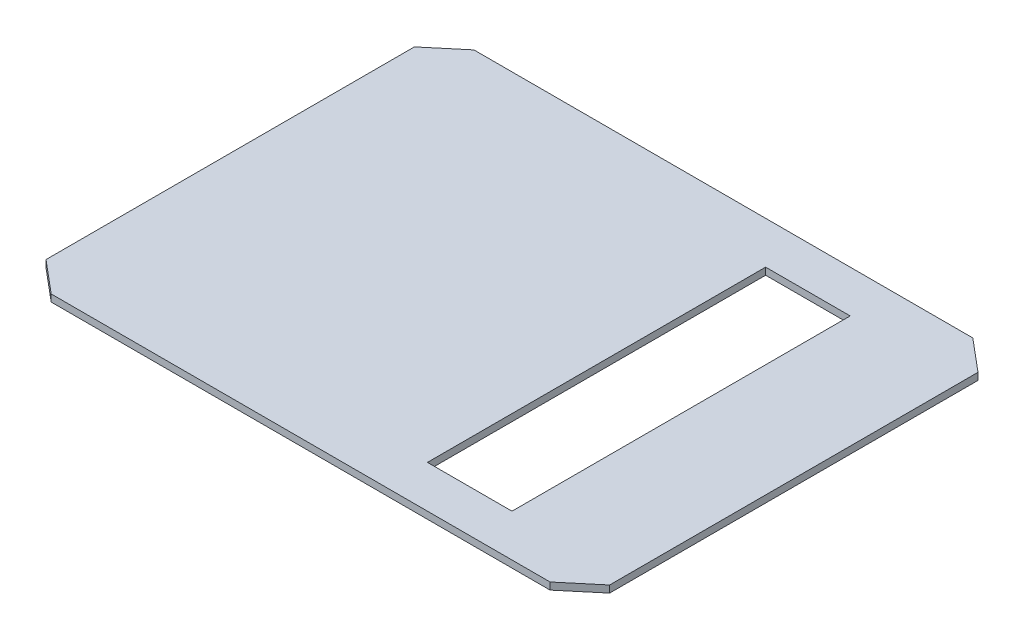
SolidWorks part; units mm, degrees
material "Thornel Mat VMA"
ref_plane "Front Plane" through (0, 0, 0) normal (0, 0, 1) x (1, 0, 0)
ref_plane "Top Plane" through (0, 0, 0) normal (0, 1, 0) x (1, 0, 0)
ref_plane "Right Plane" through (0, 0, 0) normal (1, 0, 0) x (0, 0, -1)
sketch "Sketch1" plane through (0, 0, 0) normal (0, 1, 0) x (1, 0, 0)
  line L0 (0, -95.25) -> (0, 95.25) construction
  line L1 (-127, 95.25) -> (127, 95.25) construction
  line L2 (-127, 95.25) -> (-127, -95.25) construction
  line L3 (-127, -95.25) -> (127, -95.25) construction
  line L4 (127, 95.25) -> (127, -95.25) construction
  line L5 (-127, 0) -> (127, 0) construction
  line L6 (-114.3, 0) -> (-114.3, 52.7344) construction
  line L7 (-114.3, 52.7344) -> (-101.6, 52.7344) construction
  line L8 (-101.6, 52.7344) -> (-87.0069, 64.9795) construction
  line L9 (-87.0069, 64.9795) -> (-87.0069, 76.2) construction
  line L10 (-87.0069, 76.2) -> (0, 76.2) construction
  line L11 (-127, 83.0049) -> (-112.4069, 95.25) construction
  line L12 (-87.0069, 64.9795) -> (-112.4069, 95.25) construction
  line L13 (-101.6, 52.7344) -> (-127, 83.0049) construction
  line L15 (-127, 95.25) -> (127, 95.25) construction
  line L16 (-127, 95.25) -> (-127, -95.25) construction
  line L17 (-127, -95.25) -> (127, -95.25) construction
  line L18 (127, 95.25) -> (127, -95.25) construction
  line L19 (-127, 95.25) -> (127, -95.25) construction
  line L20 (-127, -95.25) -> (127, 95.25) construction
  line L22 (127, -83.0049) -> (112.4069, -95.25)
  line L23 (-127, -83.0049) -> (-112.4069, -95.25)
  line L24 (-112.4069, 95.25) -> (112.4069, 95.25)
  line L25 (-127, -83.0049) -> (-127, 83.0049)
  line L26 (127, 83.0049) -> (127, -83.0049)
  line L27 (112.4069, -95.25) -> (-112.4069, -95.25)
  line L28 (-94.3034, 58.8569) -> (-119.7034, 89.1274) construction
  line L33 (-127, 83.0049) -> (-112.4069, 95.25)
  line L36 (127, 83.0049) -> (112.4069, 95.25)
  point P8 (0, 0)
  point P18 (0, 0)
  dimension "D1" = 190.5
  dimension "D2" = 254
  dimension "D3" = 12.7
  dimension "D4" = 19.05
  dimension "D5" = 12.7
  dimension "D6" = 40
  dimension "D7" = 19.05
  dimension "D8" = 0
  dimension "D9" = 12.7
extrude "Boss-Extrude1" add sketch "Sketch1" along normal blind 3.175 contours L27 L22 L26 L36 L24 L33 L25 L23 region at (0, 0, 0)
sketch "Sketch2" plane through (0, 3.175, 0) normal (0, 1, 0) x (1, 0, 0)
  line L0 (0, 0) -> (127, 0) construction
  line L1 (127, 83.0049) -> (127, -83.0049) construction
  line L3 (38.1, 76.2) -> (76.2, 76.2)
  line L4 (38.1, 76.2) -> (38.1, -76.2)
  line L5 (38.1, -76.2) -> (76.2, -76.2)
  line L6 (76.2, 76.2) -> (76.2, -76.2)
  line L7 (38.1, 76.2) -> (76.2, -76.2) construction
  line L8 (38.1, -76.2) -> (76.2, 76.2) construction
  point P5 (57.15, 0)
  dimension "D1" = 38.1
  dimension "D2" = 152.4
  dimension "D3" = 50.8
extrude "Cut-Extrude1" cut sketch "Sketch2" against normal through all
